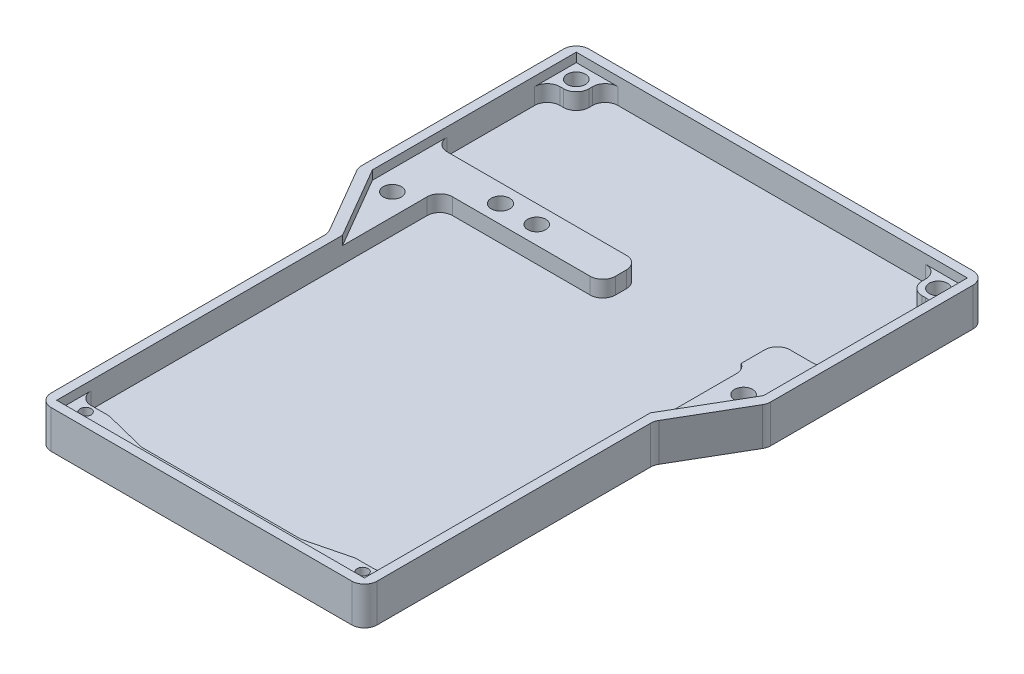
SolidWorks part; units mm, degrees
ref_plane "Front Plane" through (0, 0, 0) normal (0, 0, 1) x (1, 0, 0)
ref_plane "Top Plane" through (0, 0, 0) normal (0, 1, 0) x (1, 0, 0)
ref_plane "Right Plane" through (0, 0, 0) normal (1, 0, 0) x (0, 0, -1)
sketch "Sketch1" plane through (0, 0, 0) normal (0, 1, 0) x (1, 0, 0)
  line L0 (-57.5973, -8.4441) -> (-46.0973, -28.1941)
  line L1 (-46.0973, 51.8059) -> (43.9027, 51.8059)
  line L2 (-46.0973, 51.8059) -> (-46.0973, -108.1941)
  line L3 (-46.0973, -108.1941) -> (43.9027, -108.1941)
  line L4 (43.9027, 51.8059) -> (43.9027, -108.1941)
  line L5 (-57.5973, 51.8059) -> (55.4027, 51.8059)
  line L6 (-57.5973, 51.8059) -> (-57.5973, -8.4441)
  line L7 (-57.5973, -8.4441) -> (55.4027, -8.4441)
  line L8 (55.4027, 51.8059) -> (55.4027, -8.4441)
  line L9 (-57.5973, -8.4441) -> (-46.0973, -8.4441)
  line L10 (-46.0973, -8.4441) -> (-46.0973, -28.1941)
  line L11 (43.9027, -28.1941) -> (43.9027, -8.4441)
  line L12 (43.9027, -8.4441) -> (55.4027, -8.4441)
  line L13 (43.9027, -28.1941) -> (55.4027, -8.4441)
  point P12 (-1.0973, 51.8059)
  point P13 (-1.0973, 51.8059)
  dimension "D1" = 90
  dimension "D2" = 160
  dimension "D3" = 99.75
  dimension "D4" = 113
extrude "Boss-Extrude1" add sketch "Sketch1" along normal blind 3.5 contours L8 L5 L4 L7 | L2 L7 L4 L1 | L6 L7 L2 L5 | L7 L0 L2 | L7 L2 L3 L4 | L4 L13 L7 | L6 L5 L8 L7 | L12 L11 L13 region at (-49.9306, 0, 15.0275) region at (-51.8473, 0, -21.6809) region at (-1.0973, 0, 58.3191) region at (-1.0973, 0, -21.6809) region at (47.736, 0, 15.0275) region at (49.6527, 0, -21.6809)
sketch "Sketch2" plane through (0, 3.5, 0) normal (0, 1, 0) x (1, 0, 0)
  line L0 (-46.0973, -108.1941) -> (43.9027, -108.1941)
  line L9 (43.9027, -108.1941) -> (43.9027, -28.1941)
  line L10 (43.9027, -28.1941) -> (55.4027, -8.4441)
  line L11 (55.4027, -8.4441) -> (55.4027, 51.8059)
  line L12 (55.4027, 51.8059) -> (-57.5973, 51.8059)
  line L13 (-57.5973, 51.8059) -> (-57.5973, -8.4441)
  line L14 (-57.5973, -8.4441) -> (-46.0973, -28.1941)
  line L15 (-46.0973, -28.1941) -> (-46.0973, -108.1941)
  line L16 (-43.5973, -105.6941) -> (41.4027, -105.6941)
  line L17 (41.4027, -105.6941) -> (41.4027, -26.7384)
  line L18 (41.4027, -26.7384) -> (52.9027, -6.9884)
  line L19 (52.9027, -6.9884) -> (52.9027, 49.3059)
  line L20 (52.9027, 49.3059) -> (-55.0973, 49.3059)
  line L21 (-55.0973, 49.3059) -> (-55.0973, -6.9884)
  line L22 (-55.0973, -6.9884) -> (-43.5973, -26.7384)
  line L23 (-43.5973, -26.7384) -> (-43.5973, -105.6941)
  line L24 (43.9027, -28.1941) -> (41.4027, -28.1941)
  line L25 (41.4027, -28.1941) -> (41.4027, -26.7384)
  line L26 (43.9027, -28.1941) -> (41.4027, -26.7384)
  line L27 (52.9027, -6.9884) -> (55.4027, -6.9884)
  line L28 (55.4027, -6.9884) -> (55.4027, -8.4441)
  line L29 (52.9027, -6.9884) -> (55.4027, -8.4441)
  line L30 (55.4027, -6.9884) -> (55.4027, -8.4441)
  line L31 (-55.0973, -6.9884) -> (-57.5973, -6.9884)
  line L32 (-57.5973, -6.9884) -> (-57.5973, -8.4441)
  line L33 (-57.5973, -8.4441) -> (-55.0973, -6.9884)
  line L34 (-43.5973, -26.7384) -> (-46.0973, -28.1941)
  line L35 (-46.0973, -28.1941) -> (-43.5973, -28.1941)
  line L36 (-43.5973, -28.1941) -> (-43.5973, -26.7384)
  line L37 (-57.5973, -6.9884) -> (-57.5973, -8.4441)
  dimension "D1" = 2.5
  dimension "D2" = 2.5
  dimension "D3" = 2.5
  dimension "D4" = 90
  dimension "D5" = 90
  dimension "D6" = 2.5
  dimension "D7" = 2.5
  dimension "D8" = 90
  dimension "D9" = 90
extrude "Boss-Extrude2" add sketch "Sketch2" along normal blind 7 contours L35 L15 L0 L9 L24 L17 L16 L23 | L29 L18 L26 L10 | L24 L26 L17 | L27 L29 L11 | L31 L21 L20 L19 L27 L11 L12 L13 | L34 L35 L23 | L34 L22 L33 L14 | L13 L33 L31 region at (-44.8932, 3.5, 68.1941) region at (-50.5973, 3.5, 17.5913) region at (-44.4306, 3.5, 27.7089) region at (48.4027, 3.5, 17.5913) region at (42.236, 3.5, 27.7089) region at (-56.764, 3.5, 7.4737) region at (54.5694, 3.5, 7.4737) region at (-56.3235, 3.5, -22.4087)
sketch "Sketch3" plane through (0, 3.5, 0) normal (0, 1, 0) x (1, 0, 0)
  line L0 (41.4027, -105.6941) -> (41.4027, 49.3059) construction
  line L1 (-43.5973, -105.6941) -> (41.4027, -105.6941)
  line L2 (-43.5973, -105.6941) -> (-43.5973, -99.6941)
  line L3 (-43.5973, -99.6941) -> (41.4027, -99.6941)
  line L4 (41.4027, -105.6941) -> (41.4027, -99.6941)
  line L5 (-35.0973, -99.6941) -> (-23.0973, -102.6941)
  line L6 (-23.0973, -102.6941) -> (20.9027, -102.6941)
  line L7 (20.9027, -102.6941) -> (32.9027, -99.6941)
  line L8 (-35.0973, -99.6941) -> (-35.0973, -105.6941)
  line L9 (-35.0973, -105.6941) -> (32.9027, -105.6941)
  line L10 (32.9027, -105.6941) -> (32.9027, -99.6941)
  line L11 (55.4027, 51.8059) -> (-57.5973, 51.8059) construction
  line L12 (-55.0973, 49.3059) -> (-47.0973, 49.3059)
  line L13 (-55.0973, 49.3059) -> (-55.0973, 41.3059)
  line L14 (-55.0973, 41.3059) -> (-47.0973, 41.3059)
  line L15 (-47.0973, 49.3059) -> (-47.0973, 41.3059)
  line L16 (52.9027, 49.3059) -> (44.9027, 49.3059)
  line L17 (52.9027, 49.3059) -> (52.9027, 41.3059)
  line L18 (52.9027, 41.3059) -> (44.9027, 41.3059)
  line L19 (44.9027, 49.3059) -> (44.9027, 41.3059)
  circle A0 centre (-39.3473, -101.9441) radius 1.5
  circle A1 centre (37.1527, -101.9441) radius 1.5
  circle A2 centre (-51.0973, 45.3059) radius 2.5
  circle A3 centre (48.9027, 45.3059) radius 2.5
  point P32 (-55.0973, 45.3059)
  point P33 (-51.0973, 41.3059)
  point P34 (48.9027, 41.3059)
  point P35 (44.9027, 45.3059)
  dimension "D4" = 3
  dimension "D7" = 3
  dimension "D17" = 5
  dimension "D18" = 5
  dimension "D1" = 6
  dimension "D2" = 4.25
  dimension "D3" = 3.75
  dimension "D5" = 76.5
  dimension "D6" = 4.25
  dimension "D8" = 12
  dimension "D9" = 12
  dimension "D10" = 3
  dimension "D11" = 8.5
  dimension "D12" = 8.5
  dimension "D13" = 8
  dimension "D14" = 8
  dimension "D15" = 8
  dimension "D16" = 8
  dimension "D19" = 6.5
extrude "Boss-Extrude3" add sketch "Sketch3" along normal blind 4.5 contours L8 L3 A0 | L1 L10 L7 L6 L5 L8 | L10 L3 A1 | L13 L12 L15 L14 | L17 L16 L19 L18 | A2 | A3 region at (-43.4933, 3.5, 102.6941) region at (-1.0973, 3.5, 103.8191) region at (33.0067, 3.5, 102.6941)
sketch "Sketch4" plane through (0, 3.5, 0) normal (0, 1, 0) x (1, 0, 0)
  line L0 (-43.5973, 49.3059) -> (-43.5973, -99.6941) construction
  line L1 (-43.5973, 10.1309) -> (1.4027, 10.1309)
  line L2 (-43.5973, 10.1309) -> (-43.5973, 0.1309)
  line L3 (-43.5973, 0.1309) -> (1.4027, 0.1309)
  line L4 (1.4027, 10.1309) -> (1.4027, 0.1309)
  line L5 (41.4027, 49.3059) -> (-43.5973, 49.3059) construction
  line L6 (41.4027, -99.6941) -> (41.4027, 49.3059) construction
  line L7 (1.4027, 10.1309) -> (-43.5973, 10.1309)
  line L8 (1.4027, 10.1309) -> (1.4027, 49.3059)
  line L9 (1.4027, 49.3059) -> (-43.5973, 49.3059)
  line L10 (-43.5973, 10.1309) -> (-43.5973, 49.3059)
  line L11 (39.6145, 10.1309) -> (41.4027, 10.1309)
  line L12 (39.6145, 10.1309) -> (39.6145, 0.1309)
  line L13 (39.6145, 0.1309) -> (41.4027, 0.1309)
  line L14 (41.4027, 10.1309) -> (41.4027, 0.1309)
  line L15 (-55.0973, 49.3059) -> (-55.0973, -6.9884) construction
  line L16 (-43.5973, 0.1309) -> (-55.0973, 0.1309)
  line L17 (-43.5973, 0.1309) -> (-43.5973, 10.1309)
  line L18 (-43.5973, 10.1309) -> (-55.0973, 10.1309)
  line L19 (-55.0973, 0.1309) -> (-55.0973, 10.1309)
  line L20 (52.9027, -6.9884) -> (52.9027, 49.3059) construction
  line L21 (41.4027, 10.1309) -> (52.9027, 10.1309)
  line L22 (41.4027, 10.1309) -> (41.4027, 0.1309)
  line L23 (41.4027, 0.1309) -> (52.9027, 0.1309)
  line L24 (52.9027, 10.1309) -> (52.9027, 0.1309)
  line L25 (-43.5973, -26.7384) -> (-43.5973, 0.1309)
  line L26 (-55.0973, 0.1309) -> (-55.0973, -6.9884)
  line L27 (-55.0973, -6.9884) -> (-43.5973, -26.7384)
  line L28 (-43.5973, 0.1309) -> (-55.0973, 0.1309)
  line L29 (41.4027, -26.7384) -> (41.4027, 0.1309)
  line L30 (52.9027, 0.1309) -> (41.4027, 0.1309)
  line L31 (52.9027, 0.1309) -> (52.9027, -6.9884)
  line L32 (52.9027, -6.9884) -> (52.8628, -7.0199)
  line L33 (41.4027, -26.7384) -> (52.9027, -6.9884)
  circle A0 centre (-31.8473, 5.1309) radius 2.5
  circle A1 centre (-21.8473, 5.1309) radius 2.5
  dimension "D3" = 5
  dimension "D4" = 5
  dimension "D1" = 11.75
  dimension "D2" = 21.75
  dimension "D5" = 10
  dimension "D6" = 5
  dimension "D7" = 5
  dimension "D8" = 44.175
  dimension "D9" = 45
extrude "Boss-Extrude4" add sketch "Sketch4" along normal up to surface (4.5 mm away) contours L4 L1 L3 A1 A0 | L26 L27 L25 L16 | L29 L33 L31 L23 | L12 L11 L14 L13 | L17 L16 L19 L18 | L22 L21 L24 L23 region at (-21.0973, 3.5, -9.6699) region at (-48.2336, 3.5, 9.3226) region at (46.039, 3.5, 9.3226) up to face at (-51.0973, 8, -45.3059)
sketch "Sketch5" plane through (0, 5, 0) normal (0, 1, 0) x (1, 0, 0)
  line L0 (-55.0973, 10.1309) -> (-55.0973, -6.9884) construction
  line L1 (52.9027, -6.9884) -> (52.9027, 10.1309) construction
  circle A0 centre (-21.8473, 5.1309) radius 2.5
  circle A1 centre (-31.8473, 5.1309) radius 2.5593
  circle A2 centre (-39.3473, -101.9441) radius 1.5
  circle A3 centre (37.1527, -101.9441) radius 1.5
  circle A4 centre (-51.0973, 45.3059) radius 2.5
  circle A5 centre (48.9027, 45.3059) radius 2.5
  circle A6 centre (-49.5973, -6.9884) radius 2.5
  circle A7 centre (47.4027, -6.9884) radius 2.5
  point P26 (0, 0)
  point P28 (0, 0)
  point P30 (0, 0)
  dimension "D1" = 5
  dimension "D2" = 5
  dimension "D3" = 5.5
  dimension "D4" = 5.5
extrude "Cut-Extrude1" cut sketch "Sketch5" against normal through all both and the other way through all
fillet "Fillet1" radius 3.5 27 edges at (-46.0973, 5.25, 28.1941) (-57.5973, 5.25, 8.4441) (-57.5973, 5.25, -51.8059) (55.4027, 5.25, -51.8059) (55.4027, 5.25, 8.4441) (43.9027, 5.25, 28.1941) (-55.0973, 5.75, -41.3059) (-47.0973, 5.75, -49.3059) (-47.0973, 5.75, -41.3059) (44.9027, 5.75, -49.3059) (44.9027, 5.75, -41.3059) (52.9027, 5.75, -41.3059) (-55.0973, 5.75, -10.1309) (-43.5973, 5.75, -0.1309) (1.4027, 5.75, -10.1309) (1.4027, 5.75, -0.1309) (52.9027, 5.75, -10.1309) (39.6145, 5.75, -10.1309) (41.4027, 5.75, -0.1309) (-46.0973, 5.25, 108.1941) (43.9027, 5.25, 108.1941) (41.4027, 5.75, 99.6941) (32.9027, 5.75, 99.6941) (20.9027, 5.75, 102.6941) (-23.0973, 5.75, 102.6941) (-43.5973, 5.75, 99.6941) (-35.0973, 5.75, 99.6941)
